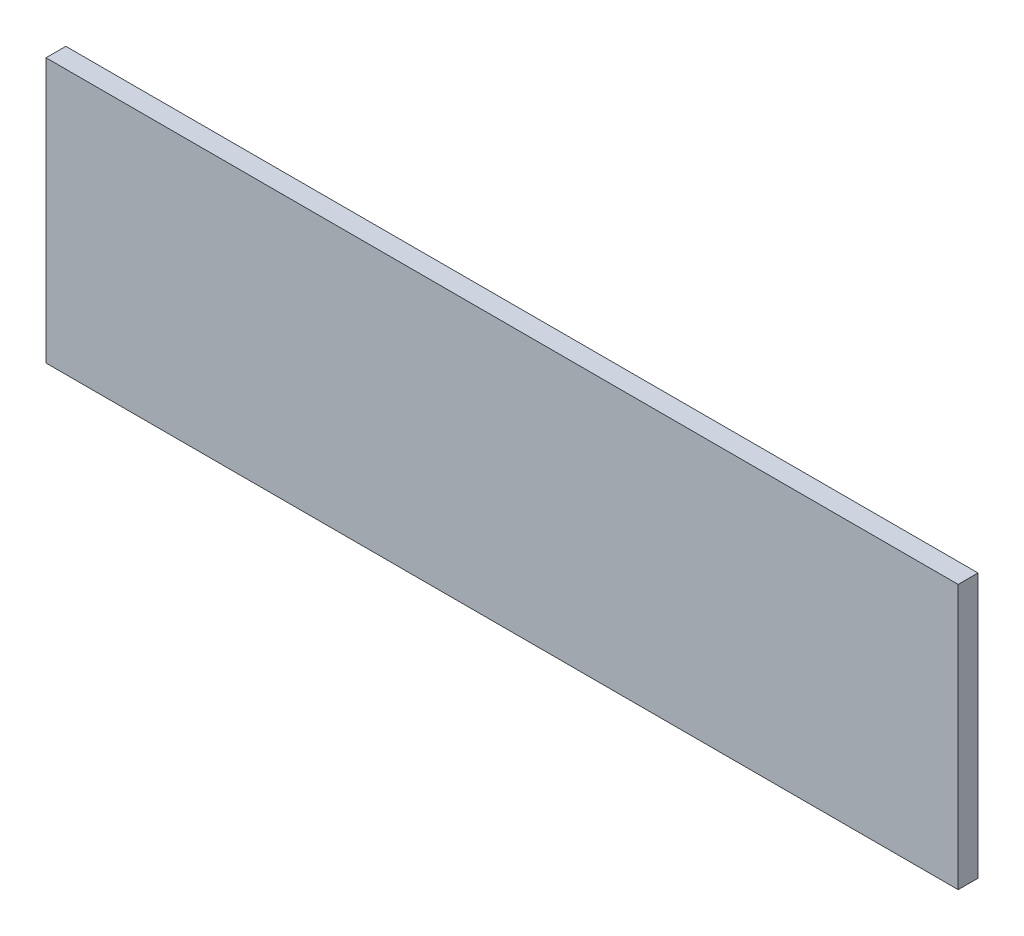
SolidWorks part; units mm, degrees
ref_plane "Alzado" through (0, 0, 0) normal (0, 0, 1) x (1, 0, 0)
ref_plane "Planta" through (0, 0, 0) normal (0, 1, 0) x (1, 0, 0)
ref_plane "Vista lateral" through (0, 0, 0) normal (1, 0, 0) x (0, 0, -1)
sketch "Croquis1" plane through (0, 0, 0) normal (0, 0, 1) x (1, 0, 0)
  line L1 (-345, -100) -> (345, -100)
  line L2 (-345, -100) -> (-345, 100)
  line L3 (-345, 100) -> (345, 100)
  line L4 (345, -100) -> (345, 100)
  line L5 (-345, -100) -> (345, 100) construction
  line L6 (-345, 100) -> (345, -100) construction
  point P0 (0, 0)
  dimension "D1" = 690
  dimension "D2" = 200
extrude "Saliente-Extruir1" add sketch "Croquis1" along normal blind 15
